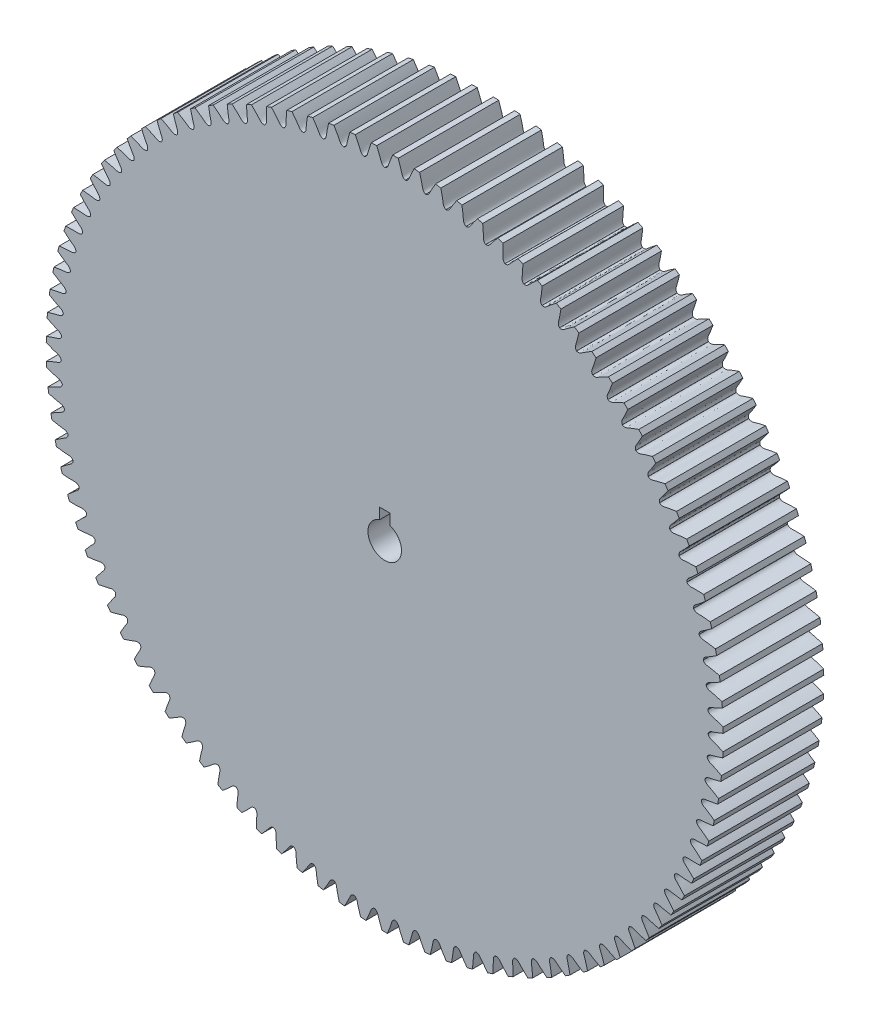
SolidWorks part; units mm, degrees
ref_plane "前视基准面" through (0, 0, 0) normal (0, 0, 1) x (1, 0, 0)
ref_plane "上视基准面" through (0, 0, 0) normal (0, 1, 0) x (1, 0, 0)
ref_plane "右视基准面" through (0, 0, 0) normal (1, 0, 0) x (0, 0, -1)
other "Configuration Table"
sketch "草图1" plane through (0, 0, 0) normal (0, 0, 1) x (1, 0, 0)
  circle A0 centre (0, 0) radius 101
extrude "凸台-拉伸1" add sketch "草图1" along normal blind 30
ref_axis "基准轴1" through (0, 0, -1.5) along (0, 0, 1)
sketch "草图2" plane through (0, 0, 0) normal (0, 0, 1) x (1, 0, 0)
  line L0 (0, 0) -> (0, 101) construction
  circle A0 centre (0, 0) radius 101 construction
  arc A1 (0.01, 96.4977) -> (-0.01, 96.4977) centre (0, 0) ccw
  arc A2 (11.8181, 114.9054) -> (-11.8181, 114.9054) centre (0, 0) ccw
  spline S0 degree 3 poles (0.01, 96.4977) (0.8807, 96.7653) (1.0817, 97.6821) (1.4803, 98.7502) (1.7232, 99.3868) (1.995, 100.0516) (2.2941, 100.7454) (2.6225, 101.4668) (2.9814, 102.2151) (3.372, 102.9893) (3.7953, 103.7884) (4.2527, 104.6115) (4.7451, 105.4573) (5.2737, 106.325) (5.8395, 107.2133) (6.4436, 108.1211) (7.0869, 109.0472) (7.7705, 109.9903) (8.4952, 110.9493) (9.262, 111.9229) (10.3573, 113.2578) (11.2213, 114.2477) (11.8181, 114.9054) knots 0 0 0 0 0.095311 0.124512 0.1554 0.187976 0.22224 0.258192 0.295831 0.335158 0.376173 0.418876 0.463267 0.509345 0.557111 0.606565 0.657707 0.710536 0.765053 0.821258 0.879151 1 1 1 1
  spline S1 degree 3 poles (-0.01, 96.4977) (-0.8807, 96.7653) (-1.0817, 97.6821) (-1.4803, 98.7502) (-1.7232, 99.3868) (-1.995, 100.0516) (-2.2941, 100.7454) (-2.6225, 101.4668) (-2.9814, 102.2151) (-3.372, 102.9893) (-3.7953, 103.7884) (-4.2527, 104.6115) (-4.7451, 105.4573) (-5.2737, 106.325) (-5.8395, 107.2133) (-6.4436, 108.1211) (-7.0869, 109.0472) (-7.7705, 109.9903) (-8.4952, 110.9493) (-9.262, 111.9229) (-10.3573, 113.2578) (-11.2213, 114.2477) (-11.8181, 114.9054) knots 0 0 0 0 0.095311 0.124512 0.1554 0.187976 0.22224 0.258192 0.295831 0.335158 0.376173 0.418876 0.463267 0.509345 0.557111 0.606565 0.657707 0.710536 0.765053 0.821258 0.879151 1 1 1 1
extrude "切除-拉伸1" cut sketch "草图2" along normal through all
pattern_circular "阵列(圆周)1" count 99 every 3.636 about axis through (0, 0, -1.5) along (0, 0, 1) of "切除-拉伸1"
sketch "草图3" plane through (0, 0, 0) normal (0, 0, 1) x (1, 0, 0)
  circle A0 centre (0, 0) radius 99 construction
  dimension "Dn" = 198
sketch "草图4" plane through (0, 0, 30) normal (0, 0, 1) x (1, 0, 0)
  line L0 (0, 0) -> (-1.5, 0)
  line L1 (-1.5, 0) -> (-1.5, 8)
  line L2 (-1.5, 8) -> (1.5, 8)
  line L3 (1.5, 8) -> (1.5, 0)
  line L4 (1.5, 0) -> (0, 0)
  circle A0 centre (0, 0) radius 5
extrude "切除-拉伸2" cut sketch "草图4" against normal through all contours A0 L3 L2 L1 | L3 A0 L1 L0 L4 | L1 A0 L3 L4 L0 region at (0, -0.5704, 30) region at (0, 2.4625, 30) region at (0, 6.4612, 30)
